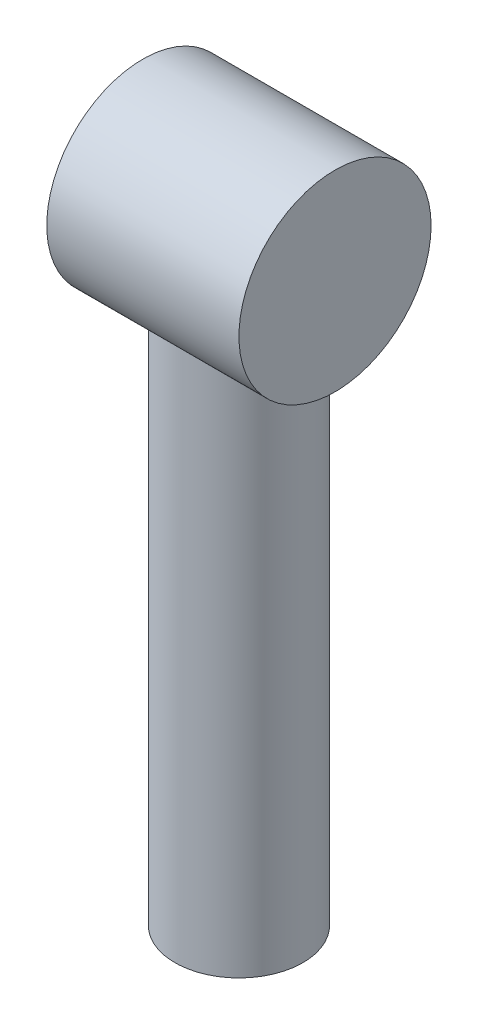
SolidWorks part; units mm, degrees
ref_plane "Front Plane" through (0, 0, 0) normal (0, 0, 1) x (1, 0, 0)
ref_plane "Top Plane" through (0, 0, 0) normal (0, 1, 0) x (1, 0, 0)
ref_plane "Right Plane" through (0, 0, 0) normal (1, 0, 0) x (0, 0, -1)
sketch "Sketch1" plane through (0, 0, 0) normal (0, 1, 0) x (1, 0, 0)
  line L3 (14.4338, 0) -> (7.2169, 12.5)
  line L4 (7.2169, 12.5) -> (-7.2169, 12.5)
  line L5 (-7.2169, 12.5) -> (-14.4338, 0)
  line L6 (-14.4338, 0) -> (-7.2169, -12.5)
  line L7 (-7.2169, -12.5) -> (7.2169, -12.5)
  line L8 (7.2169, -12.5) -> (14.4338, 0)
  circle A0 centre (0, 0) radius 20
  circle A1 centre (0, 0) radius 12.5 construction
  dimension "D1" = 40
extrude "Boss-Extrude1" add sketch "Sketch1" along normal blind 25
sketch "Sketch2" plane through (0, 0, 0) normal (0, -1, 0) x (1, 0, 0)
  circle A1 centre (0, 0) radius 20
extrude "Boss-Extrude2" add sketch "Sketch2" along normal blind 100
ref_plane "Plane1" through (20, 0, 0) normal (1, 0, 0) x (0, 0, -1)
sketch "Sketch5" plane through (0, 0, 0) normal (0, 1, 0) x (1, 0, 0)
  line L1 (14.4338, 0) -> (7.2169, 12.5)
  line L2 (7.2169, 12.5) -> (-7.2169, 12.5)
  line L3 (-7.2169, 12.5) -> (-14.4338, 0)
  line L4 (-14.4338, 0) -> (-7.2169, -12.5)
  line L5 (-7.2169, -12.5) -> (7.2169, -12.5)
  line L6 (7.2169, -12.5) -> (14.4338, 0)
  circle A0 centre (0, 0) radius 12.5 construction
sketch "Sketch6" plane through (0, 25, 0) normal (0, 1, 0) x (1, 0, 0)
  circle A0 centre (0, 0) radius 20
  dimension "D1" = 40
extrude "Boss-Extrude4" add sketch "Sketch6" against normal blind 100
sketch "Sketch7" plane through (20, 0, 0) normal (1, 0, 0) x (0, 0, -1)
  circle A2 centre (0, 39.2866) radius 25
  dimension "D3" = 50
extrude "Cut-Extrude2" cut sketch "Sketch7" against normal blind 40
sketch "Sketch8" plane through (20, 0, 0) normal (1, 0, 0) x (0, 0, -1)
  circle A0 centre (0, 39.2528) radius 25
  circle A1 centre (0, 39.2528) radius 22.5
  dimension "D1" = 50
  dimension "D2" = 45
extrude "Boss-Extrude7" add sketch "Sketch8" against normal blind 40 contours A1 | A0 region at (20, 39.2528, 0)
sketch "Sketch9" plane through (20, 0, 0) normal (1, 0, 0) x (0, 0, -1)
  circle A0 centre (0, 39.2528) radius 25
extrude "Boss-Extrude8" add sketch "Sketch9" against normal blind 2
sketch "Sketch10" plane through (18, 0, 0) normal (-1, 0, 0) x (0, 0, 1)
  line L1 (-15.0811, 22.5552) -> (15.0811, 22.5552)
  arc A1 (-15.0811, 22.5552) -> (15.0811, 22.5552) centre (0, 39.2528) ccw
extrude "Boss-Extrude10" add sketch "Sketch10" along normal blind 38
sketch "Sketch11" plane through (0, -100, 0) normal (0, -1, 0) x (1, 0, 0)
  line L0 (0, 20) -> (0, 0)
  line L1 (0, 0) -> (20, 0)
  line L2 (20, -27.5) -> (20, 27.5) construction
  line L4 (0, 14.4338) -> (-12.5, 7.2169)
  line L5 (-12.5, 7.2169) -> (-12.5, -7.2169)
  line L6 (-12.5, -7.2169) -> (0, -14.4338)
  line L7 (0, -14.4338) -> (12.5, -7.2169)
  line L8 (12.5, -7.2169) -> (12.5, 7.2169)
  line L9 (12.5, 7.2169) -> (0, 14.4338)
  arc A0 (20, 0) -> (-20, 0) centre (0, 0) ccw construction
  circle A1 centre (0, 0) radius 12.5 construction
extrude "Cut-Extrude3" cut sketch "Sketch11" against normal blind 25 contours L8 L9 L0 L1 | L7 L8 L1 L0 L4 L5 L6 region at (5.5556, -100, 5.6131) region at (-1.8519, -100, -1.871)
sketch "Sketch12" plane through (20, 0, 0) normal (1, 0, 0) x (0, 0, -1)
  circle A0 centre (0, 39.2528) radius 25
extrude "Cut-Extrude4" cut sketch "Sketch12" against normal blind 75
sketch "Sketch13" plane through (20, 0, 0) normal (1, 0, 0) x (0, 0, -1)
  circle A0 centre (0, 39.3347) radius 30
  dimension "D1" = 60
sketch "Sketch14" plane through (0, -100, 0) normal (0, -1, 0) x (1, 0, 0)
  line L1 (0, -14.4338) -> (12.5, -7.2169)
  line L2 (12.5, -7.2169) -> (12.5, 7.2169)
  line L3 (12.5, 7.2169) -> (0, 14.4338)
  line L4 (0, 14.4338) -> (-12.5, 7.2169)
  line L5 (-12.5, 7.2169) -> (-12.5, -7.2169)
  line L6 (-12.5, -7.2169) -> (0, -14.4338)
  circle A0 centre (0, 0) radius 12.5 construction
  circle A1 centre (0, 0) radius 20
extrude "Boss-Extrude11" add sketch "Sketch14" along normal blind 50
extrude "Boss-Extrude12" add sketch "Sketch13" against normal blind 50 and the other way blind 10
sketch "Sketch16" plane through (30, 0, 0) normal (1, 0, 0) x (0, 0, -1)
  line L0 (-17.3205, 17.3347) -> (17.3205, 17.3347)
  line L1 (0, 67.3347) -> (24.1903, 67.3347)
  circle A0 centre (0, 39.3347) radius 28
  dimension "D1" = 56
  dimension "D2" = 50
